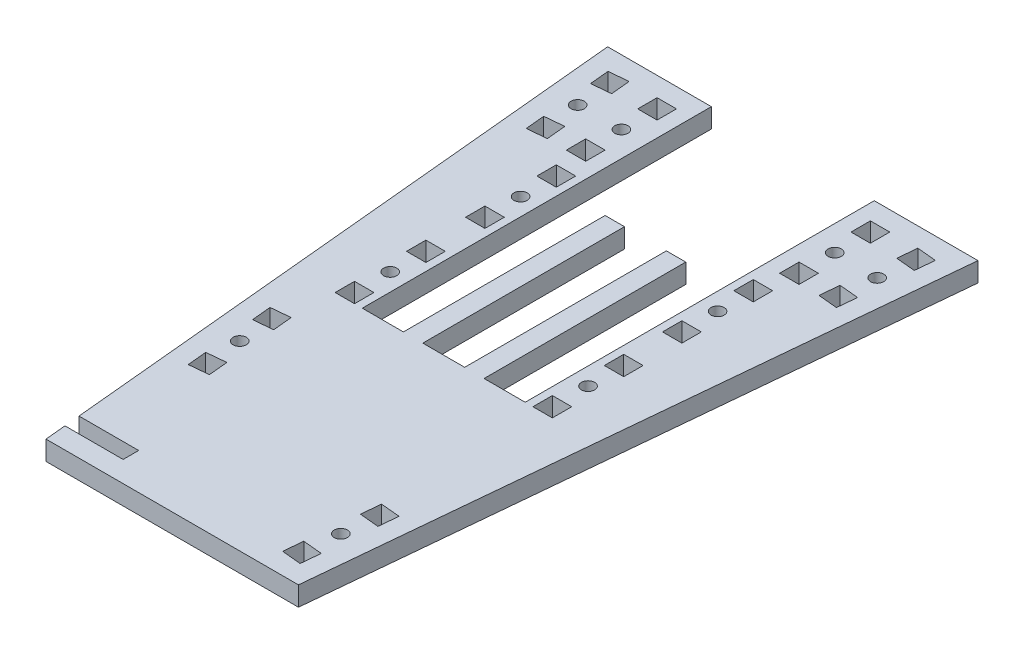
SolidWorks part; units mm, degrees
ref_plane "Front Plane" through (0, 0, 0) normal (0, 0, 1) x (1, 0, 0)
ref_plane "Top Plane" through (0, 0, 0) normal (0, 1, 0) x (1, 0, 0)
ref_plane "Right Plane" through (0, 0, 0) normal (1, 0, 0) x (0, 0, -1)
sketch "Sketch1" plane through (0, 0, 0) normal (0, 1, 0) x (1, 0, 0)
  line L0 (0, 0) -> (0, -183.008) construction
  line L1 (-47.8759, 114.3) -> (-26.67, 114.3)
  line L2 (47.8759, 114.3) -> (28.575, -88.9) construction
  line L3 (-47.8759, 114.3) -> (-28.575, -88.9) construction
  line L4 (38.1, 78.232) -> (44.45, 78.232) construction
  line L5 (-47.8759, 114.3) -> (-60.6331, 114.3)
  line L6 (-41.9836, -82.042) -> (-11.3629, -82.042) construction
  line L7 (-57.15, 0) -> (57.15, 0) construction
  line L8 (31.75, 114.3) -> (31.75, 78.232) construction
  line L9 (-31.75, 114.3) -> (-31.75, 78.232) construction
  line L10 (6.858, 66.04) -> (6.858, 0) construction
  line L11 (-6.858, 66.04) -> (-6.858, 0) construction
  line L12 (-6.858, 66.04) -> (-6.858, 0)
  line L13 (-6.858, 0) -> (6.858, 0)
  line L14 (6.858, 0) -> (6.858, 66.04)
  line L15 (6.858, 66.04) -> (13.208, 66.04)
  line L16 (-41.9836, -82.042) -> (-22.9336, -82.042)
  line L17 (-22.9336, -82.042) -> (-22.9336, -76.962)
  line L18 (13.208, 66.04) -> (13.208, 0)
  line L19 (13.208, 0) -> (26.67, 0)
  line L20 (26.67, 0) -> (26.67, 114.3)
  line L21 (26.67, 114.3) -> (47.8759, 114.3)
  line L22 (-26.67, 0) -> (-26.67, 114.3)
  line L23 (-13.208, 0) -> (-26.67, 0)
  line L24 (-13.208, 66.04) -> (-13.208, 0)
  line L25 (-6.858, 0) -> (-6.858, 66.04)
  line L26 (-13.208, 66.04) -> (-6.858, 66.04)
  line L27 (-22.9336, -76.962) -> (-42.4661, -76.962)
  line L28 (-41.9836, -82.042) -> (-41.3322, -88.9)
  line L29 (47.8759, 114.3) -> (60.6331, 114.3)
  line L30 (60.6331, 114.3) -> (41.3322, -88.9)
  line L31 (-28.575, -88.9) -> (0, -88.9)
  line L32 (0, -88.9) -> (28.575, -88.9)
  line L33 (28.575, -88.9) -> (41.3322, -88.9)
  line L34 (-60.6331, 114.3) -> (-42.4661, -76.962)
  line L35 (-28.575, -88.9) -> (-41.3322, -88.9)
  line L36 (-38.5725, -50.8) -> (-32.251, -50.1995) construction
  line L37 (34.9536, -88.9) -> (28.632, -88.2995) construction
  line L38 (35.554, -82.5785) -> (34.9536, -88.9) construction
  line L39 (-39.173, -44.4785) -> (-38.5725, -50.8) construction
  point P0 (0, 0)
  line B0 (34.925, 78.232) -> (34.925, 107.95) construction
  line B1 (32.766, 93.091) -> (37.084, 93.091) construction
  line B2 (31.75, 101.6) -> (38.1, 101.6)
  line B3 (31.75, 101.6) -> (31.75, 107.95)
  line B4 (31.75, 107.95) -> (38.1, 107.95)
  line B5 (38.1, 101.6) -> (38.1, 107.95)
  line B6 (31.75, 101.6) -> (38.1, 107.95) construction
  line B7 (31.75, 107.95) -> (38.1, 101.6) construction
  line B8 (31.75, 78.232) -> (38.1, 84.582) construction
  line B9 (31.75, 84.582) -> (38.1, 78.232) construction
  line B10 (38.1, 84.582) -> (38.1, 78.232)
  line B11 (31.75, 78.232) -> (38.1, 78.232)
  line B12 (31.75, 84.582) -> (31.75, 78.232)
  line B13 (31.75, 84.582) -> (38.1, 84.582)
  circle B14 centre (34.925, 93.091) radius 2.159
  line B15 (-34.925, 78.232) -> (-34.925, 107.95) construction
  line B16 (-32.766, 93.091) -> (-37.084, 93.091) construction
  line B17 (-31.75, 101.6) -> (-38.1, 101.6)
  line B18 (-31.75, 101.6) -> (-31.75, 107.95)
  line B19 (-31.75, 107.95) -> (-38.1, 107.95)
  line B20 (-38.1, 101.6) -> (-38.1, 107.95)
  line B21 (-31.75, 101.6) -> (-38.1, 107.95) construction
  line B22 (-31.75, 107.95) -> (-38.1, 101.6) construction
  line B23 (-31.75, 78.232) -> (-38.1, 84.582) construction
  line B24 (-31.75, 84.582) -> (-38.1, 78.232) construction
  line B25 (-38.1, 84.582) -> (-38.1, 78.232)
  line B26 (-31.75, 78.232) -> (-38.1, 78.232)
  line B27 (-31.75, 84.582) -> (-31.75, 78.232)
  line B28 (-31.75, 84.582) -> (-38.1, 84.582)
  circle B29 centre (-34.925, 93.091) radius 2.159
  line B30 (47.6261, 78.0934) -> (50.4362, 107.6782) construction
  line B31 (46.8819, 93.09) -> (51.1805, 92.6817) construction
  line B32 (46.675, 101.6569) -> (52.9966, 101.0565)
  line B33 (46.675, 101.6569) -> (47.2755, 107.9785)
  line B34 (47.2755, 107.9785) -> (53.597, 107.378)
  line B35 (52.9966, 101.0565) -> (53.597, 107.378)
  line B36 (46.675, 101.6569) -> (53.597, 107.378) construction
  line B37 (47.2755, 107.9785) -> (52.9966, 101.0565) construction
  line B38 (44.4654, 78.3936) -> (51.3873, 84.1147) construction
  line B39 (45.0658, 84.7152) -> (50.7869, 77.7932) construction
  line B40 (51.3873, 84.1147) -> (50.7869, 77.7932)
  line B41 (44.4654, 78.3936) -> (50.7869, 77.7932)
  line B42 (45.0658, 84.7152) -> (44.4654, 78.3936)
  line B43 (45.0658, 84.7152) -> (51.3873, 84.1147)
  circle B44 centre (49.0312, 92.8858) radius 2.159
  line B45 (32.3933, -82.2782) -> (35.2034, -52.6934) construction
  line B46 (31.649, -67.2817) -> (35.9476, -67.69) construction
  line B47 (31.4421, -58.7147) -> (37.7637, -59.3152)
  line B48 (31.4421, -58.7147) -> (32.0426, -52.3932)
  line B49 (32.0426, -52.3932) -> (38.3641, -52.9936)
  line B50 (37.7637, -59.3152) -> (38.3641, -52.9936)
  line B51 (31.4421, -58.7147) -> (38.3641, -52.9936) construction
  line B52 (32.0426, -52.3932) -> (37.7637, -59.3152) construction
  line B53 (29.2325, -81.978) -> (36.1545, -76.2569) construction
  line B54 (29.8329, -75.6565) -> (35.554, -82.5785) construction
  line B55 (36.1545, -76.2569) -> (35.554, -82.5785)
  line B56 (29.2325, -81.978) -> (35.554, -82.5785)
  line B57 (29.8329, -75.6565) -> (29.2325, -81.978)
  line B58 (29.8329, -75.6565) -> (36.1545, -76.2569)
  circle B59 centre (33.7983, -67.4858) radius 2.159
  line B60 (-36.0122, -44.1782) -> (-38.8223, -14.5934) construction
  line B61 (-35.2679, -29.1817) -> (-39.5666, -29.59) construction
  line B62 (-35.0611, -20.6147) -> (-41.3826, -21.2152)
  line B63 (-35.0611, -20.6147) -> (-35.6615, -14.2932)
  line B64 (-35.6615, -14.2932) -> (-41.9831, -14.8936)
  line B65 (-41.3826, -21.2152) -> (-41.9831, -14.8936)
  line B66 (-35.0611, -20.6147) -> (-41.9831, -14.8936) construction
  line B67 (-35.6615, -14.2932) -> (-41.3826, -21.2152) construction
  line B68 (-32.8514, -43.878) -> (-39.7734, -38.1569) construction
  line B69 (-33.4519, -37.5565) -> (-39.173, -44.4785) construction
  line B70 (-39.7734, -38.1569) -> (-39.173, -44.4785)
  line B71 (-32.8514, -43.878) -> (-39.173, -44.4785)
  line B72 (-33.4519, -37.5565) -> (-32.8514, -43.878)
  line B73 (-33.4519, -37.5565) -> (-39.7734, -38.1569)
  circle B74 centre (-37.4172, -29.3858) radius 2.159
  line B75 (-47.6261, 78.0934) -> (-50.4362, 107.6782) construction
  line B76 (-46.8819, 93.09) -> (-51.1805, 92.6817) construction
  line B77 (-46.675, 101.6569) -> (-52.9966, 101.0565)
  line B78 (-46.675, 101.6569) -> (-47.2755, 107.9785)
  line B79 (-47.2755, 107.9785) -> (-53.597, 107.378)
  line B80 (-52.9966, 101.0565) -> (-53.597, 107.378)
  line B81 (-46.675, 101.6569) -> (-53.597, 107.378) construction
  line B82 (-47.2755, 107.9785) -> (-52.9966, 101.0565) construction
  line B83 (-44.4654, 78.3936) -> (-51.3873, 84.1147) construction
  line B84 (-45.0658, 84.7152) -> (-50.7869, 77.7932) construction
  line B85 (-51.3873, 84.1147) -> (-50.7869, 77.7932)
  line B86 (-44.4654, 78.3936) -> (-50.7869, 77.7932)
  line B87 (-45.0658, 84.7152) -> (-44.4654, 78.3936)
  line B88 (-45.0658, 84.7152) -> (-51.3873, 84.1147)
  circle B89 centre (-49.0312, 92.8858) radius 2.159
  line B90 (32.385, 0) -> (32.385, 29.718) construction
  line B91 (30.226, 14.859) -> (34.544, 14.859) construction
  line B92 (29.21, 23.368) -> (35.56, 23.368)
  line B93 (29.21, 23.368) -> (29.21, 29.718)
  line B94 (29.21, 29.718) -> (35.56, 29.718)
  line B95 (35.56, 23.368) -> (35.56, 29.718)
  line B96 (29.21, 23.368) -> (35.56, 29.718) construction
  line B97 (29.21, 29.718) -> (35.56, 23.368) construction
  line B98 (29.21, 0) -> (35.56, 6.35) construction
  line B99 (29.21, 6.35) -> (35.56, 0) construction
  line B100 (35.56, 6.35) -> (35.56, 0)
  line B101 (29.21, 0) -> (35.56, 0)
  line B102 (29.21, 6.35) -> (29.21, 0)
  line B103 (29.21, 6.35) -> (35.56, 6.35)
  circle B104 centre (32.385, 14.859) radius 2.159
  line B105 (32.385, 42.418) -> (32.385, 72.136) construction
  line B106 (30.226, 57.277) -> (34.544, 57.277) construction
  line B107 (29.21, 65.786) -> (35.56, 65.786)
  line B108 (29.21, 65.786) -> (29.21, 72.136)
  line B109 (29.21, 72.136) -> (35.56, 72.136)
  line B110 (35.56, 65.786) -> (35.56, 72.136)
  line B111 (29.21, 65.786) -> (35.56, 72.136) construction
  line B112 (29.21, 72.136) -> (35.56, 65.786) construction
  line B113 (29.21, 42.418) -> (35.56, 48.768) construction
  line B114 (29.21, 48.768) -> (35.56, 42.418) construction
  line B115 (35.56, 48.768) -> (35.56, 42.418)
  line B116 (29.21, 42.418) -> (35.56, 42.418)
  line B117 (29.21, 48.768) -> (29.21, 42.418)
  line B118 (29.21, 48.768) -> (35.56, 48.768)
  circle B119 centre (32.385, 57.277) radius 2.159
  line B120 (-32.385, 0) -> (-32.385, 29.718) construction
  line B121 (-30.226, 14.859) -> (-34.544, 14.859) construction
  line B122 (-29.21, 23.368) -> (-35.56, 23.368)
  line B123 (-29.21, 23.368) -> (-29.21, 29.718)
  line B124 (-29.21, 29.718) -> (-35.56, 29.718)
  line B125 (-35.56, 23.368) -> (-35.56, 29.718)
  line B126 (-29.21, 23.368) -> (-35.56, 29.718) construction
  line B127 (-29.21, 29.718) -> (-35.56, 23.368) construction
  line B128 (-29.21, 0) -> (-35.56, 6.35) construction
  line B129 (-29.21, 6.35) -> (-35.56, 0) construction
  line B130 (-35.56, 6.35) -> (-35.56, 0)
  line B131 (-29.21, 0) -> (-35.56, 0)
  line B132 (-29.21, 6.35) -> (-29.21, 0)
  line B133 (-29.21, 6.35) -> (-35.56, 6.35)
  circle B134 centre (-32.385, 14.859) radius 2.159
  line B135 (-32.385, 42.6931) -> (-32.385, 72.4111) construction
  line B136 (-30.226, 57.5521) -> (-34.544, 57.5521) construction
  line B137 (-29.21, 66.0611) -> (-35.56, 66.0611)
  line B138 (-29.21, 66.0611) -> (-29.21, 72.4111)
  line B139 (-29.21, 72.4111) -> (-35.56, 72.4111)
  line B140 (-35.56, 66.0611) -> (-35.56, 72.4111)
  line B141 (-29.21, 66.0611) -> (-35.56, 72.4111) construction
  line B142 (-29.21, 72.4111) -> (-35.56, 66.0611) construction
  line B143 (-29.21, 42.6931) -> (-35.56, 49.0431) construction
  line B144 (-29.21, 49.0431) -> (-35.56, 42.6931) construction
  line B145 (-35.56, 49.0431) -> (-35.56, 42.6931)
  line B146 (-29.21, 42.6931) -> (-35.56, 42.6931)
  line B147 (-29.21, 49.0431) -> (-29.21, 42.6931)
  line B148 (-29.21, 49.0431) -> (-35.56, 49.0431)
  circle B149 centre (-32.385, 57.5521) radius 2.159
  dimension "D1" = 63.5
  dimension "D2" = 6.35
  dimension "D3" = 6.858
  dimension "D4" = 57.15
  dimension "D5" = 6.858
  dimension "D6" = 5.08
  dimension "D7" = 48.26
  dimension "D8" = 203.2
  dimension "D9" = 6.35
  dimension "D10" = 6.35
  dimension "D11" = 5.08
  dimension "D12" = 114.3
  dimension "D13" = 6.35
  dimension "D14" = 6.35
  dimension "D15" = 38.1
  dimension "D16" = 2.54
  dimension "D17" = 93.1039
  dimension "D18" = 131.3754
  dimension "D19" = 19.05
  dimension "D20" = 12.7
sketch_block_instance "Female T-Slot Assembly-1"
sketch_block "Female T-Slot Assembly" parameters "D4"=4.318, "D1"=6.35, "D2"=6.35, "D3"=6.35
sketch_block_instance "Female T-Slot Assembly-3"
sketch_block_instance "Female T-Slot Assembly-1"
sketch_block_instance "Female T-Slot Assembly-14"
sketch_block_instance "Female T-Slot Assembly-16"
sketch_block_instance "Female T-Slot Assembly-17"
sketch_block_instance "Female T-Slot Assembly-1"
sketch_block_instance "Female T-Slot Assembly-19"
sketch_block_instance "Female T-Slot Assembly-24"
sketch_block_instance "Female T-Slot Assembly-25"
extrude "Boss-Extrude1" add sketch "Sketch1" along normal blind 6.35 contours L26 L24 L23 L22 L1 L21 L20 L19 L18 L15 L14 L13 L12 B29 B28 B27 B26 B25 B12 B13 B10 B11 B5 B2 B3 region at (-37.273, 0, -111.9337)
equation "\"Ball Diameter\"= 1.75in"
equation "\"Ball Radius\" = \"Ball Diameter\"/2"
equation "\"Sheet Thickness\"= 0.25in"
equation "\"Screw Diameter\"= .17in"
equation "\"Robot Diameter\"= 14in"
equation "\"Castor Screw Diameter\"= 0.22in"
equation "\"Wheel Diameter\" = 4in"
equation "\"Nut Diameter\" = 8.4mm"
equation "\"Nut Height\" = 2.9mm"
equation "\"Screw Height\" = 0.55in"
equation "\"Pulley Diameter\" = 1in"
equation "\"Reactor Height\" = 14in"
equation "\"Elevator Height\" = 11.5in"
equation "\"Elevator Width\" = \"Ball Diameter\" + 0.25in"
equation "\"Elevator Bearing Diameter\" = sqr(2*(\"Sheet Thickness\"^2)) + 0.2in"
equation "\"Elevator Axle Endcap Diameter\" = \"Pulley Diameter\" + 0.25in"
equation "\"Elevator Axle Length\" = \"Elevator Width\" + 8*\"Sheet Thickness\""
equation "\"Elevator Clearance from Axis\" = 3.5in"
equation "\"Elevator Horizontal Clearance\" = \"Elevator Width\" + 0.5in"
equation "\"Claw Horizontal Seperation\" = (\"Elevator Width\"/2) - (1.5 * \"Sheet Thickness\") - 0.15in"
equation "\"Claw Radius\" = \"Ball Radius\" + 0.1in"
equation "\"Castor Wheel Height\" = 1.25in"
equation "\"Length of Chute\" = 8in"
equation "\"D4@Sketch1\"=\"Ball Diameter\" + 0.5in"
equation "\"D8@Sketch1\"=\"Length of Chute\""
